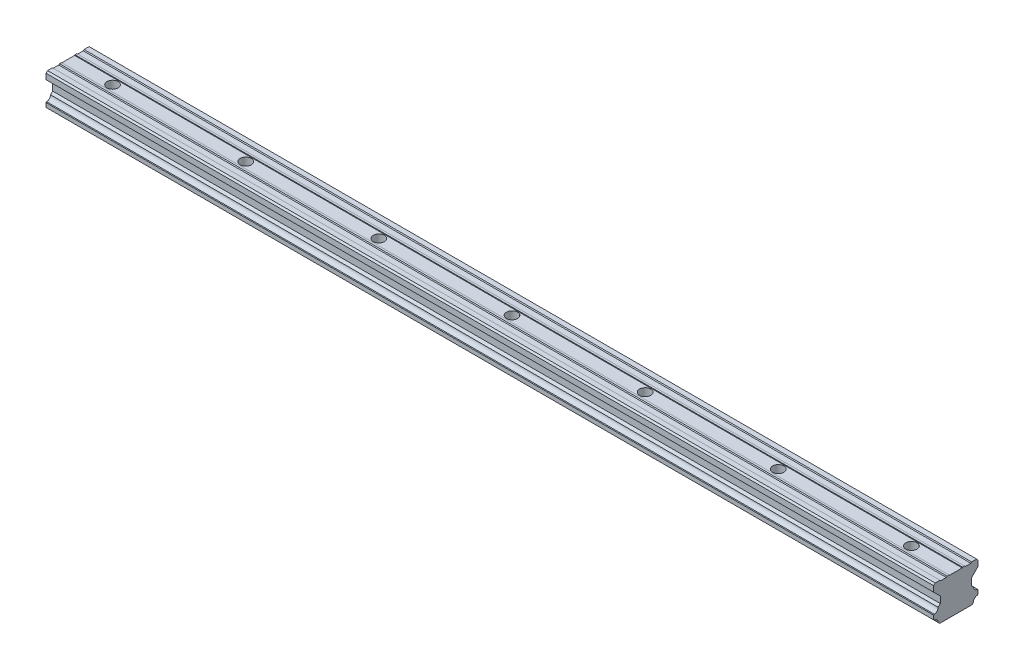
SolidWorks part; units mm, degrees
material "AISI 1020 Steel, Cold Rolled"
ref_plane "Front Plane" through (0, 0, 0) normal (0, 0, 1) x (1, 0, 0)
ref_plane "Top Plane" through (0, 0, 0) normal (0, 1, 0) x (1, 0, 0)
ref_plane "Right Plane" through (0, 0, 0) normal (1, 0, 0) x (0, 0, -1)
sketch "Sketch1" plane through (0, 0, 0) normal (1, 0, 0) x (0, 0, -1)
  line L0 (-7.9658, -7.694) -> (-7.2663, -8.3935)
  line L1 (-7.2663, -8.3935) -> (7.2663, -8.3935)
  line L2 (7.2663, -8.3935) -> (7.9658, -7.694)
  line L3 (9.7474, -5.9133) -> (10, -5.6608)
  line L4 (10, -5.6608) -> (10, -3.7884)
  line L5 (10, -3.7884) -> (9.7474, -3.5358)
  line L6 (7.9658, -1.7232) -> (7.0051, -0.7626)
  line L7 (7.0051, -0.7626) -> (7.0051, 2.1662)
  line L8 (7.0051, 2.1662) -> (10, 5.1611)
  line L9 (10, 5.1611) -> (10, 7.7124)
  line L10 (10, 7.7124) -> (9.4085, 8.3935)
  line L11 (9.4085, 8.3935) -> (7.133, 8.3935)
  line L12 (7.133, 8.3935) -> (6.7895, 8.05)
  line L13 (6.7895, 8.05) -> (4.2711, 8.05)
  line L14 (4.2711, 8.05) -> (3.9277, 8.3935)
  line L15 (3.9277, 8.3935) -> (3.0613, 8.3935)
  line L16 (3.0613, 8.3935) -> (2.872, 8.2042)
  line L17 (2.872, 8.2042) -> (-2.872, 8.2042)
  line L18 (-2.872, 8.2042) -> (-3.0613, 8.3935)
  line L19 (-3.0613, 8.3935) -> (-3.9277, 8.3935)
  line L20 (-3.9277, 8.3935) -> (-4.2712, 8.05)
  line L21 (-4.2712, 8.05) -> (-6.7895, 8.05)
  line L22 (-6.7895, 8.05) -> (-7.133, 8.3935)
  line L23 (-7.133, 8.3935) -> (-9.3077, 8.3935)
  line L24 (-9.3077, 8.3935) -> (-10, 7.7012)
  line L25 (-10, 7.7012) -> (-10, 5.1611)
  line L26 (-10, 5.1611) -> (-7.0051, 2.1662)
  line L27 (-7.0051, 2.1662) -> (-7.0051, -0.7626)
  line L28 (-7.0051, -0.7626) -> (-7.9658, -1.7232)
  line L29 (-9.7474, -5.9133) -> (-10, -5.6608)
  line L30 (-10, -5.6608) -> (-10, -3.7884)
  line L31 (-10, -3.7884) -> (-9.7474, -3.5358)
  arc A0 (-7.9658, -7.694) -> (-9.7474, -5.9133) centre (-9.7035, -7.6511) ccw
  arc A1 (-9.7474, -3.5358) -> (-7.9658, -1.7232) centre (-9.7025, -1.7981) ccw
  arc A2 (7.9658, -1.7232) -> (9.7474, -3.5358) centre (9.7025, -1.7981) ccw
  arc A3 (9.7474, -5.9133) -> (7.9658, -7.694) centre (9.7035, -7.6511) ccw
extrude "Boss-Extrude1" add sketch "Sketch1" along normal blind 400
sketch "Sketch2" plane through (0, -8.3935, 0) normal (0, -1, 0) x (1, 0, 0)
  circle A0 centre (20, 0) radius 3
  dimension "D1" = 6
  dimension "D2" = 20
hole_wizard "Hole1" positions "3DSketch1" profile "Sketch3" legacy end condition through all
sketch3d "3DSketch1"
  point P0 (20, -8.3935, 0)
sketch "Sketch3" plane through (20, -8.3935, 0) normal (1, 0, 0) x (0, 0, -1)
  line L0 (0, 0) -> (0, 16.7869)
  line L1 (0, 16.7869) -> (2.5, 16.7869)
  line L2 (2.5, 16.7869) -> (2.5, 8.5)
  line L3 (2.5, 8.5) -> (4.5, 8.5)
  line L4 (4.5, 8.5) -> (4.5, 0)
  line L5 (4.5, 0) -> (0, 0)
  line L6 (0, 110) -> (0, -10) construction
  dimension "Diameter" = 5
  dimension "Depth" = 16.7869
  dimension "C-Bore Diameter" = 9
  dimension "C-Bore Depth" = 8.5
sketch "Sketch4" plane through (0, -8.3935, 0) normal (0, -1, 0) x (-1, 0, 0)
  line L0 (0, 0) -> (-400, 0) construction
  line L1 (-400, -7.2663) -> (-400, 7.2663) construction
pattern_linear "LPattern1" count 7 spacing 60 along (1, 0, 0) of "Hole1"
